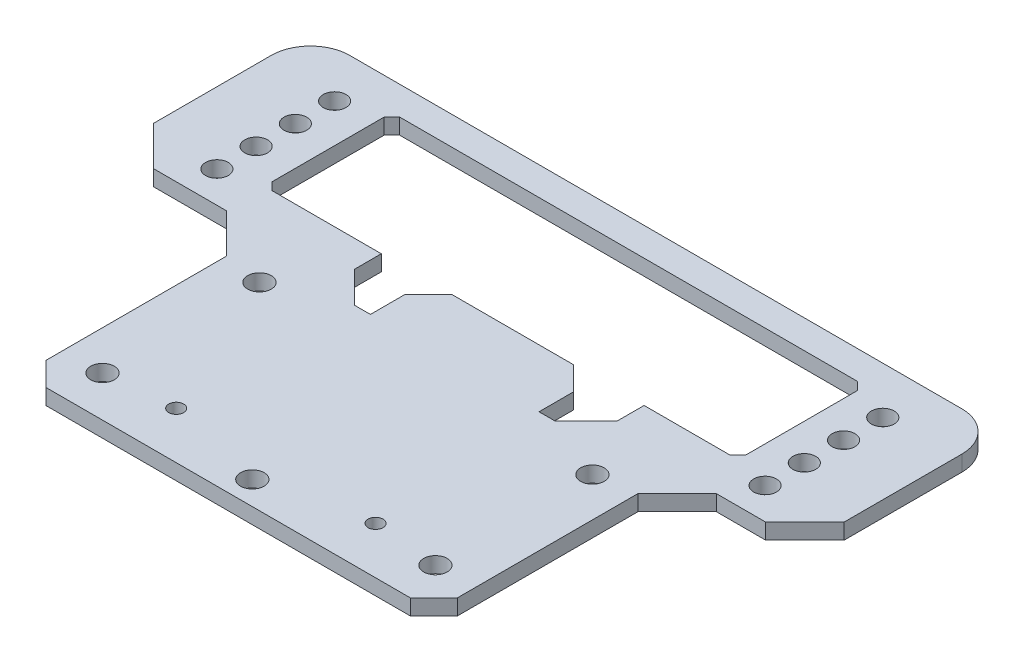
SolidWorks part; units mm, degrees
ref_plane "Front Plane" through (0, 0, 0) normal (0, 0, 1) x (1, 0, 0)
ref_plane "Top Plane" through (0, 0, 0) normal (0, 1, 0) x (1, 0, 0)
ref_plane "Right Plane" through (0, 0, 0) normal (1, 0, 0) x (0, 0, -1)
sketch "Sketch2" plane through (0, 0, 0) normal (0, 1, 0) x (1, 0, 0)
  line L1 (-35, 25) -> (35, 25)
  line L2 (-35, 25) -> (-35, -25)
  line L3 (-35, -25) -> (35, -25)
  line L4 (35, 25) -> (35, -25)
  line L5 (-35, 25) -> (35, -25) construction
  line L6 (-35, -25) -> (35, 25) construction
  point P0 (0, 0)
  dimension "D1" = 50
  dimension "D2" = 70
extrude "Boss-Extrude1" add sketch "Sketch2" along normal blind 2
sketch "Sketch3" plane through (0, 2, 0) normal (0, 1, 0) x (1, 0, 0)
  line L0 (-35, -25) -> (35, -25) construction
  line L1 (-35, 25) -> (-22, 25)
  line L2 (-35, 25) -> (-35, -25)
  line L3 (-35, -25) -> (-22, -25)
  line L4 (-22, 25) -> (-22, -25)
  line L6 (35, 25) -> (22, 25)
  line L7 (35, 25) -> (35, -25)
  line L8 (35, -25) -> (22, -25)
  line L9 (22, 25) -> (22, -25)
extrude "Cut-Extrude1" cut sketch "Sketch3" against normal through all
ref_plane "Plane1" through (22, 2, 25) normal (1, 0, 0) x (0, 0, -1)
sketch "Sketch9" plane through (0, 2, 0) normal (0, 1, 0) x (1, 0, 0)
  line L0 (-22, -25) -> (-22, 25) construction
  line L1 (-22, 25) -> (22, 25)
  line L2 (-22, 25) -> (-22, 31)
  line L3 (-22, 31) -> (22, 31)
  line L4 (22, 25) -> (22, 31)
  line L5 (-22, 10.4486) -> (-33, 10.4486)
  line L6 (-22, 10.4486) -> (-22, 31)
  line L7 (-22, 31) -> (-33, 31)
  line L8 (-33, 10.4486) -> (-33, 31)
  line L10 (22, 31) -> (33, 31)
  line L11 (22, 31) -> (22, 10.4486)
  line L12 (22, 10.4486) -> (33, 10.4486)
  line L13 (33, 31) -> (33, 10.4486)
  dimension "D1" = 6
  dimension "D2" = 11
  dimension "D3" = 11
extrude "Extrude-Thin1" add sketch "Sketch9" against normal blind 2 thin contours L3 thin type one direction wall 10
sketch "Sketch13" plane through (0, 2, 0) normal (0, 1, 0) x (1, 0, 0)
sketch "Sketch14" plane through (0, 2, 0) normal (0, 1, 0) x (1, 0, 0)
sketch "Sketch15" plane through (0, 2, 0) normal (0, 1, 0) x (1, 0, 0)
  line L1 (-30, 26.4189) -> (30, 26.4189)
  line L2 (-30, 26.4189) -> (-30, 11.4189)
  line L3 (-30, 11.4189) -> (30, 11.4189)
  line L4 (30, 26.4189) -> (30, 11.4189)
  dimension "D1" = 60
extrude "Cut-Extrude2" cut sketch "Sketch15" against normal through all
chamfer "Chamfer1" distance 1 angle 45 rebuild error yes
sketch "Sketch17" plane through (0, 2, 0) normal (0, 1, 0) x (1, 0, 0)
sketch "Sketch20" plane through (0, 2, 0) normal (0, 1, 0) x (1, 0, 0)
  line L1 (-22, 31) -> (-44, 31)
  line L2 (-22, 31) -> (-22, 6)
  line L3 (-22, 6) -> (-44, 6)
  line L4 (-44, 31) -> (-44, 6)
  line L5 (22, 31) -> (44, 31)
  line L6 (22, 31) -> (22, 6)
  line L7 (22, 6) -> (44, 6)
  line L8 (44, 31) -> (44, 6)
  dimension "D1" = 25
  dimension "D2" = 25
  dimension "D3" = 22
  dimension "D4" = 22
extrude "Boss-Extrude5" add sketch "Sketch20" against normal through all
sketch "Sketch21" plane through (0, 2, 0) normal (0, 1, 0) x (1, 0, 0)
  line L1 (-30, 27.3746) -> (30.3345, 27.3746)
  line L2 (-30, 27.3746) -> (-30, 11.1231)
  line L3 (-30, 11.1231) -> (30.3345, 11.1231)
  line L4 (30.3345, 27.3746) -> (30.3345, 11.1231)
extrude "Cut-Extrude3" cut sketch "Sketch21" against normal through all
chamfer "Chamfer5" distance 1 angle 45 4 edges at (-30, 1, -27.3746) (-30, 1, -11.1231) (30.3345, 1, -11.1231) (30.3345, 1, -27.3746)
sketch "Sketch22" plane through (0, 2, 0) normal (0, 1, 0) x (1, 0, 0)
  line L1 (-22, 6) -> (-24.7, 6)
  line L2 (-22, 6) -> (-22, -25)
  line L3 (-22, -25) -> (-24.7, -25)
  line L4 (-24.7, 6) -> (-24.7, -25)
  line L5 (22, 6) -> (27.7219, 6)
  line L6 (22, 6) -> (22, -25)
  line L7 (22, -25) -> (27.7219, -25)
  line L8 (27.7219, 6) -> (27.7219, -25)
extrude "Boss-Extrude6" add sketch "Sketch22" against normal through all
chamfer "Chamfer6" distance 5 angle 45 4 edges at (-24.7, 1, -6) (-44, 1, -6) (27.7219, 1, -6) (44, 1, -6)
fillet "Fillet2" radius 5 2 edges at (-44, 1, -31) (44, 1, -31)
chamfer "Chamfer8" distance 3 angle 45 2 edges at (27.7219, 1, 25) (-24.7, 1, 25)
sketch "Sketch23" plane through (0, 2, 0) normal (0, 1, 0) x (1, 0, 0)
  line L0 (-29, 11.1231) -> (29.3345, 11.1231) construction
  line L1 (-9.0956, 3.7335) -> (-15.0956, 3.7335)
  line L2 (-9.0956, 3.7335) -> (-9.0956, 11.1231)
  line L3 (-9.0956, 11.1231) -> (-15.0956, 11.1231)
  line L4 (-15.0956, 3.7335) -> (-15.0956, 11.1231)
  line L6 (12.3886, 3.7335) -> (18.3886, 3.7335)
  line L7 (12.3886, 3.7335) -> (12.3886, 11.1231)
  line L8 (12.3886, 11.1231) -> (18.3886, 11.1231)
  line L9 (18.3886, 3.7335) -> (18.3886, 11.1231)
  dimension "D1" = 6
  dimension "D2" = 6
extrude "Cut-Extrude4" cut sketch "Sketch23" against normal through all
sketch "Sketch24" plane through (0, 2, 0) normal (0, 1, 0) x (1, 0, 0)
  line L0 (-11.6114, -22) -> (14.7886, -22) construction
  circle A0 centre (1.5886, -22) radius 1.5
  dimension "D1" = 3
extrude "Cut-Extrude5" cut sketch "Sketch24" against normal through all
chamfer "Chamfer11" distance 3 angle 45 2 edges at (-9.0956, 1, -11.1231) (12.3886, 1, -11.1231)
ref_plane "Plane2" through (18.3886, 0, -3.7335) normal (0, 1, 0) x (1, 0, 0)
chamfer "Chamfer12" distance 4 angle 45 2 edges at (-15.0956, 1, -3.7335) (18.3886, 1, -3.7335)
sketch "Sketch25" plane through (0, 2, 0) normal (0, 1, 0) x (1, 0, 0)
  circle A0 centre (-34.925, 25) radius 1.45
  circle A1 centre (-34.925, 20) radius 1.45
  circle A2 centre (-34.925, 15) radius 1.45
  circle A3 centre (-34.925, 10) radius 1.45
  circle A4 centre (34.925, 25) radius 1.45
  circle A5 centre (34.925, 20) radius 1.45
  circle A6 centre (34.925, 15) radius 1.45
  circle A7 centre (34.925, 10) radius 1.45
extrude "Cut-Extrude6" cut sketch "Sketch25" against normal through all
sketch "Sketch26" plane through (0, 2, 0) normal (0, 1, 0) x (1, 0, 0)
  circle A0 centre (-11.1114, -19) radius 0.95
  circle A1 centre (14.2886, -19) radius 0.95
extrude "Cut-Extrude7" cut sketch "Sketch26" against normal through all
sketch "Sketch27" plane through (0, 2, 0) normal (0, 1, 0) x (1, 0, 0)
  circle A0 centre (-19.7, 0.2) radius 1.5
  circle A1 centre (-19.7, -19.8) radius 1.5
  circle A2 centre (22.7219, 0.2) radius 1.5
  circle A3 centre (22.7219, -19.8) radius 1.5
extrude "Cut-Extrude8" cut sketch "Sketch27" against normal through all
